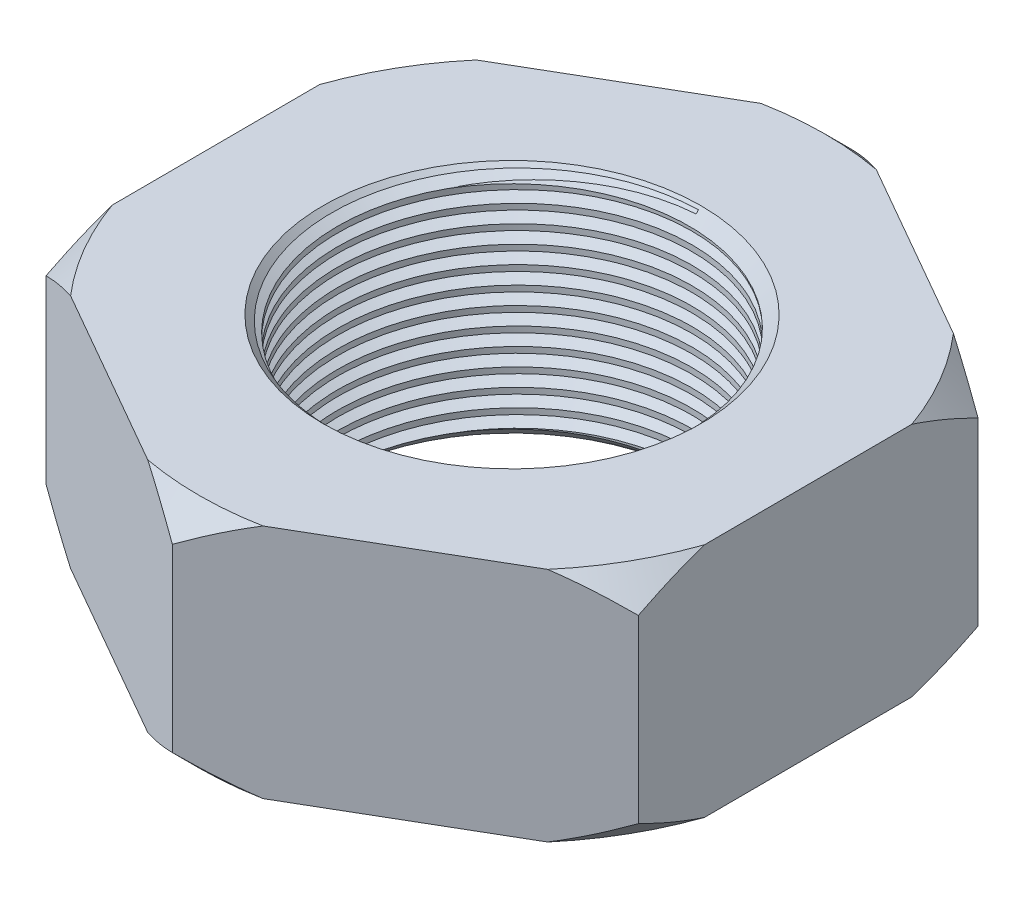
SolidWorks part; units mm, degrees
ref_plane "Front Plane" through (0, 0, 0) normal (0, 0, 1) x (1, 0, 0)
ref_plane "Top Plane" through (0, 0, 0) normal (0, 1, 0) x (1, 0, 0)
ref_plane "Right Plane" through (0, 0, 0) normal (1, 0, 0) x (0, 0, -1)
sketch "Sketch1" plane through (0, 0, 0) normal (0, 1, 0) x (1, 0, 0)
  line L1 (-25.05, 14.3468) -> (-24.9497, -14.5205)
  line L2 (-24.9497, -14.5205) -> (0.1003, -28.8673)
  line L3 (0.1003, -28.8673) -> (25.05, -14.3468)
  line L4 (25.05, -14.3468) -> (24.9497, 14.5205)
  line L5 (24.9497, 14.5205) -> (-0.1003, 28.8673)
  line L6 (-0.1003, 28.8673) -> (-25.05, 14.3468)
  circle A0 centre (0, 0) radius 25 construction
  circle A1 centre (0, 0) radius 15
extrude "Boss-Extrude1" add sketch "Sketch1" along normal blind 20
chamfer "Chamfer1" distance 1 angle 45 2 edges at (0, 20, 15) (0, 0, 15)
sketch "Sketch3" plane through (0, 0, 0) normal (1, 0, 0) x (0, 0, -1)
  line L0 (-28.8673, 20) -> (-28.8673, 17.6414)
  line L1 (-28.8673, 20) -> (-28.8673, 0) construction
  line L2 (-28.8673, 17.6414) -> (-26.5088, 20)
  line L3 (-28.8673, 20) -> (-14.3468, 20) construction
  line L4 (-26.5088, 20) -> (-28.8673, 20)
  line L5 (0, -7.1548) -> (0, 27.1548) construction
  line L6 (0, 10) -> (-43.5776, 10) construction
  line L7 (-28.8673, 0) -> (-14.3468, 0) construction
  line L8 (-26.5088, 0) -> (-28.8673, 0)
  line L9 (-28.8673, 2.3586) -> (-26.5088, 0)
  line L10 (-28.8673, 0) -> (-28.8673, 2.3586)
  dimension "D1" = 10
revolve "Cut-Revolve1" cut sketch "Sketch3" angle 360 about L5
sketch "Sketch5" plane through (0, 0, 0) normal (1, 0, 0) x (0, 0, -1)
  line L0 (0, 0) -> (0, 1) construction
  line L1 (0, -0.4613) -> (0, 0) construction
  line L2 (-15, 1) -> (15, 1) construction
  line L3 (0, 0) -> (-26.5088, 0) construction
  line L4 (0, 0) -> (0, -32.78) construction
  line L5 (0, 1) -> (-15, 1) construction
  line L6 (-15, 1) -> (-15, 0) construction
ref_plane "Plane1" through (0, 1, 0) normal (0, -1, 0) x (-1, 0, 0)
sketch "Sketch6" plane through (0, 1, 0) normal (0, -1, 0) x (-1, 0, 0)
  circle A0 centre (0, 0) radius 15
curve "Helix/Spiral1" pitch 1.5 height 18 turns 12
ref_plane "Plane2" through (0, 0, 0) normal (1, 0, 0) x (0, 0, -1)
sketch "Sketch7" plane through (0, 0, 0) normal (1, 0, 0) x (0, 0, -1)
  line L0 (-15, 0.5) -> (-15, 1.5)
  line L2 (-15, 1.5) -> (-15.866, 1)
  line L3 (-15.866, 1) -> (-15, 0.5)
  point P4 (-15, 1)
  dimension "D1" = 1
sweep "Cut-Sweep1" cut profiles "Sketch7" path "Helix/Spiral1"
